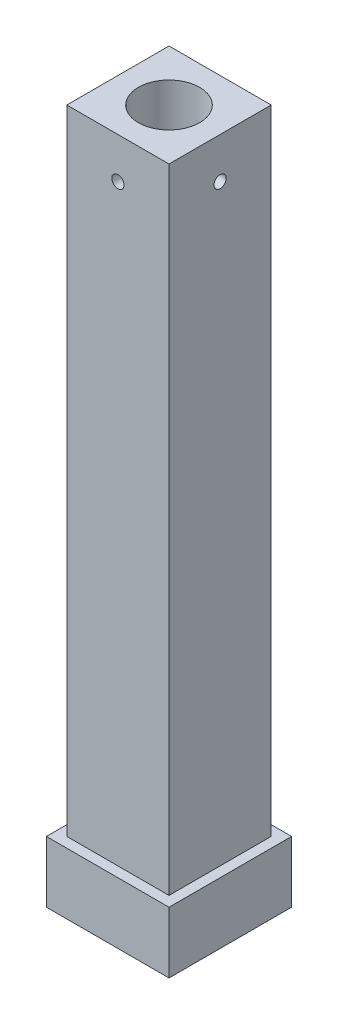
SolidWorks part; units mm, degrees
ref_plane "前视基准面" through (0, 0, 0) normal (0, 0, 1) x (1, 0, 0)
ref_plane "上视基准面" through (0, 0, 0) normal (0, 1, 0) x (1, 0, 0)
ref_plane "右视基准面" through (0, 0, 0) normal (1, 0, 0) x (0, 0, -1)
other "Configuration Table"
sketch "草图1" plane through (0, 0, 0) normal (0, 1, 0) x (1, 0, 0)
  line L1 (2.8868, 0) -> (1.4434, 2.5)
  line L2 (1.4434, 2.5) -> (-1.4434, 2.5)
  line L3 (-1.4434, 2.5) -> (-2.8868, 0)
  line L4 (-2.8868, 0) -> (-1.4434, -2.5)
  line L5 (-1.4434, -2.5) -> (1.4434, -2.5)
  line L6 (1.4434, -2.5) -> (2.8868, 0)
  line L7 (-2.5, -2.5) -> (2.5, -2.5)
  line L8 (-2.5, -2.5) -> (-2.5, 2.5)
  line L9 (-2.5, 2.5) -> (2.5, 2.5)
  line L10 (2.5, -2.5) -> (2.5, 2.5)
  line L11 (-2.5, -2.5) -> (2.5, 2.5) construction
  line L12 (-2.5, 2.5) -> (2.5, -2.5) construction
  line L13 (-3, -3) -> (3, -3)
  line L14 (-3, -3) -> (-3, 3)
  line L15 (-3, 3) -> (3, 3)
  line L16 (3, -3) -> (3, 3)
  line L17 (-3, -3) -> (3, 3) construction
  line L18 (-3, 3) -> (3, -3) construction
  circle A0 centre (0, 0) radius 2.5 construction
  circle A1 centre (0, 0) radius 1.5
  dimension "D1" = 5
  dimension "D3" = 3
  dimension "D2" = 5
  dimension "D4" = 6
extrude "凸台-拉伸1" add sketch "草图1" along normal blind 34 contours L9 L10 L7 L8
extrude "凸台-拉伸2" add sketch "草图1<5>" along normal blind 3 contours L15 L16 L13 L14
sketch "草图1<5>" plane through (0, 0, 0) normal (0, 1, 0) x (1, 0, 0) same geometry as "草图1"
extrude "切除-拉伸1" cut sketch "草图1<3>" along normal through all contours A1 region at (0, 0, 0)
sketch "草图1<3>" plane through (0, 0, 0) normal (0, 1, 0) x (1, 0, 0) same geometry as "草图1"
extrude "切除-拉伸2" cut sketch "草图1<4>" along normal blind 2 contours L1 L2 L3 L4 L5 L6
sketch "草图1<4>" plane through (0, 0, 0) normal (0, 1, 0) x (1, 0, 0) same geometry as "草图1"
sketch "草图3" plane through (0, 0, 2.5) normal (0, 0, 1) x (1, 0, 0)
  line L0 (-2.5, 34) -> (2.5, 34) construction
  line L1 (-2.5, 32) -> (2.5, 32) construction
  line L2 (-2.5, 34) -> (-2.5, 3) construction
  line L3 (2.5, 34) -> (2.5, 3) construction
  circle A0 centre (0, 32) radius 0.3
  dimension "D1" = 0.6
  dimension "D2" = 2
extrude "切除-拉伸3" cut sketch "草图3" against normal through all
sketch "草图4" plane through (-2.5, 0, 0) normal (-1, 0, 0) x (0, 0, 1)
  line L0 (-2.5, 32) -> (2.5, 32) construction
  line L1 (-2.5, 34) -> (-2.5, 3) construction
  line L2 (2.5, 34) -> (2.5, 3) construction
  line L3 (2.5, 34) -> (-2.5, 34) construction
  circle A0 centre (0, 32) radius 0.3
  dimension "D1" = 0.6
  dimension "D2" = 2
extrude "切除-拉伸4" cut sketch "草图4" against normal through all
